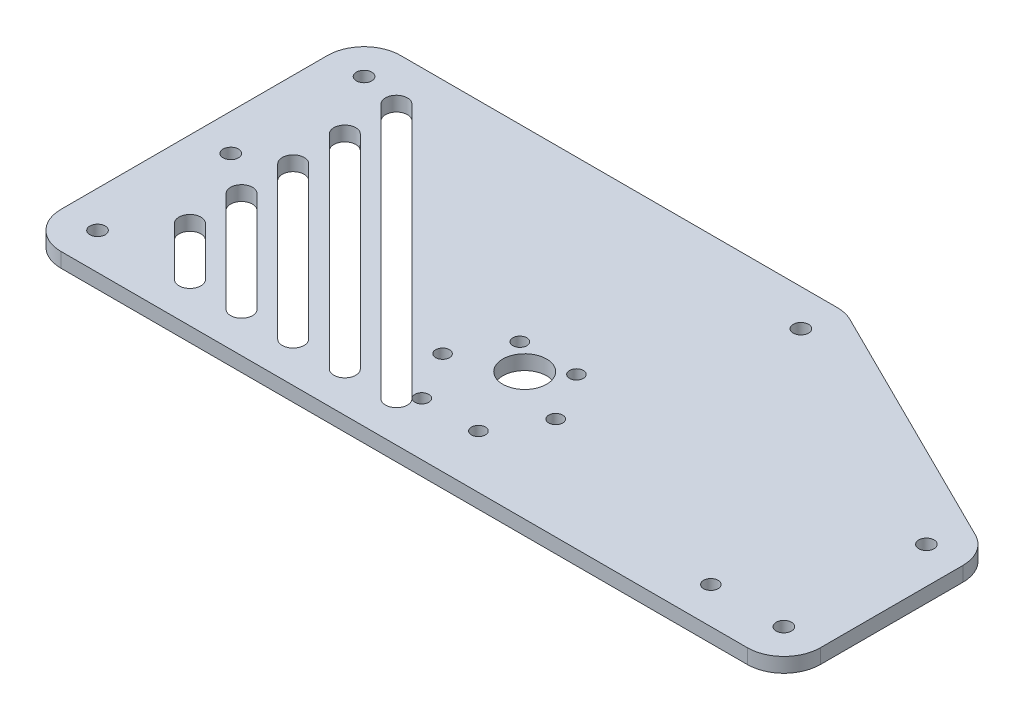
SolidWorks part; units mm, degrees
ref_plane "Front Plane" through (0, 0, 0) normal (1, 0, 0) x (0, 1, 0)
ref_plane "Top Plane" through (0, 0, 0) normal (0, 0, 1) x (0, 1, 0)
ref_plane "Right Plane" through (0, 0, 0) normal (0, 1, 0) x (-1, 0, 0)
sketch "Sketch1" plane through (0, 0, 0) normal (0, 1, 0) x (-1, 0, 0)
  line L3 (192.4493, -35) -> (72.7965, -35)
  line L4 (68.3472, -33.9557) -> (0, 0)
  line L6 (70.4493, 58) -> (70.4493, -35) construction
  line L7 (136.4493, 58) -> (136.4493, -35) construction
  line L8 (4.4493, 58) -> (70.4493, 58)
  line L9 (70.4493, 58) -> (136.4493, 58)
  line L10 (136.4493, 58) -> (192.4493, 58)
  line L11 (202.4493, 8) -> (-5.5507, 8) construction
  line L12 (-5.5507, 28) -> (202.4493, 28) construction
  line L13 (202.4493, 48) -> (202.4493, 28)
  line L14 (202.4493, 28) -> (202.4493, 8)
  line L15 (202.4493, 8) -> (202.4493, -25)
  line L16 (-5.5507, 48) -> (-5.5507, 28)
  line L17 (-5.5507, 28) -> (-5.5507, 8.9557)
  arc A0 (-5.5507, 48) -> (4.4493, 58) centre (4.4493, 48) cw
  arc A1 (-5.5507, 8.9557) -> (0, 0) centre (4.4493, 8.9557) ccw
  arc A3 (72.7965, -35) -> (68.3472, -33.9557) centre (72.7965, -25) cw
  arc A4 (202.4493, -25) -> (192.4493, -35) centre (192.4493, -25) cw
  arc A5 (192.4493, 58) -> (202.4493, 48) centre (192.4493, 48) cw
  point P16 (-5.5507, 58)
  point P19 (0, 0)
  point P27 (202.4493, -35)
  point P30 (202.4493, 58)
  dimension "D8" = 10
  dimension "D1" = 66
  dimension "D4" = 20
  dimension "D5" = 30
  dimension "D2" = 76
  dimension "D3" = 43
  dimension "D6" = 58
extrude "Boss-Extrude1" add sketch "Sketch1" along normal blind 4
sketch "Sketch2" plane through (0, 0, 0) normal (0, -1, 0) x (1, 0, 0)
  line L2 (-202.707, 11.5) -> (-191.0536, 11.5) construction
  line L3 (-118.9427, 30.8759) -> (-118.9427, 40.9875) construction
  line L4 (5.5507, 48) -> (5.5507, 8.9557) construction
  line L5 (-72.7965, -35) -> (-192.4493, -35) construction
  line L6 (-192.4493, 58) -> (-4.4493, 58) construction
  line L7 (-81.9427, 21.6542) -> (-81.9427, 50021.6542) construction
  line L9 (-181.4493, 19.5477) -> (-153.997, 47) construction
  line L10 (-183.5706, 21.669) -> (-156.1183, 49.1213)
  line L11 (-179.328, 17.4264) -> (-151.8757, 44.8787)
  line L12 (-181.4493, 5.4056) -> (-139.8549, 47) construction
  line L13 (-183.5706, 7.5269) -> (-141.9762, 49.1213)
  line L14 (-179.328, 3.2843) -> (-137.7335, 44.8787)
  line L15 (-181.4493, -8.7365) -> (-125.7127, 47) construction
  line L16 (-183.5706, -6.6152) -> (-127.8341, 49.1213)
  line L17 (-179.328, -10.8579) -> (-123.5914, 44.8787)
  line L18 (-181.4493, -22.8787) -> (-111.5706, 47) construction
  line L19 (-183.5706, -20.7574) -> (-113.6919, 49.1213)
  line L20 (-179.328, -25) -> (-109.4493, 44.8787)
  line L21 (-184.4493, 60.5499) -> (-184.4493, -43.895) construction
  line L22 (-186.5394, 50) -> (-97.1183, 50) construction
  line L23 (-108.5706, -40.8731) -> (-108.5706, -145.318) construction
  line L24 (-181.4493, 33.6899) -> (-168.1391, 47) construction
  line L25 (-165.6018, 31.1525) -> (-162.7734, 28.3241) construction
  line L26 (-158.5308, 24.0815) -> (-155.7023, 21.253) construction
  line L27 (-151.4597, 17.0104) -> (-148.6313, 14.182) construction
  line L28 (-183.5706, 35.8112) -> (-170.2605, 49.1213)
  line L29 (-179.328, 31.5685) -> (-166.0178, 44.8787)
  line L30 (-169.8445, 35.3952) -> (-172.6729, 38.2236) construction
  circle A0 centre (-192.4493, 48) radius 2.1
  circle A1 centre (-192.4493, -25) radius 2.1
  circle A2 centre (-192.4493, 11.5) radius 2.1
  circle A3 centre (-4.4493, 48) radius 2.1
  circle A4 centre (-4.4493, 8.9557) radius 2.1
  circle A5 centre (-72.7965, -25) radius 2.1
  circle A7 centre (-100.4427, 23) radius 6
  circle A9 centre (-100.4427, 30) radius 18.5 construction
  arc A11 (-183.5706, 21.669) -> (-179.328, 17.4264) centre (-181.4493, 19.5477) ccw
  arc A12 (-151.8757, 44.8787) -> (-156.1183, 49.1213) centre (-153.997, 47) ccw
  arc A13 (-183.5706, 7.5269) -> (-179.328, 3.2843) centre (-181.4493, 5.4056) ccw
  arc A14 (-137.7335, 44.8787) -> (-141.9762, 49.1213) centre (-139.8549, 47) ccw
  arc A15 (-183.5706, -6.6152) -> (-179.328, -10.8579) centre (-181.4493, -8.7365) ccw
  arc A16 (-123.5914, 44.8787) -> (-127.8341, 49.1213) centre (-125.7127, 47) ccw
  arc A17 (-183.5706, -20.7574) -> (-179.328, -25) centre (-181.4493, -22.8787) ccw
  arc A18 (-109.4493, 44.8787) -> (-113.6919, 49.1213) centre (-111.5706, 47) ccw
  arc A19 (-183.5706, 35.8112) -> (-179.328, 31.5685) centre (-181.4493, 33.6899) ccw
  arc A20 (-166.0178, 44.8787) -> (-170.2605, 49.1213) centre (-168.1391, 47) ccw
  circle A21 centre (-100.4427, 30) radius 15.5 construction
  circle A22 centre (-115.9427, 30) radius 1.9
  circle A23 centre (-108.1927, 43.4234) radius 1.9
  circle A24 centre (-92.6927, 43.4234) radius 1.9
  circle A25 centre (-84.9427, 30) radius 1.9
  circle A26 centre (-92.6927, 16.5766) radius 1.9
  circle A27 centre (-108.1927, 16.5766) radius 1.9
  circle A28 centre (-24.4493, 48) radius 2
  point P19 (-59.7454, 23)
  point P20 (-4.4493, 48)
  point P24 (-174.7942, 40.3449)
  point P27 (-24.4493, 79.1894)
  point P33 (-97.4924, -16.2986)
  point P37 (-24.4493, 47)
  point P45 (-167.7231, 33.2739)
  point P50 (-160.6521, 26.2028)
  point P57 (-153.581, 19.1317)
  point P64 (-146.5099, 12.0607)
  dimension "D5" = 30
  dimension "D1" = 4.2
  dimension "D14" = 31
  dimension "D15" = 3.8
  dimension "D2" = 37
  dimension "D6" = 12
  dimension "D7" = 45
  dimension "D8" = 6
  dimension "D9" = 8
  dimension "D10" = 8
  dimension "D11" = 4
  dimension "D12" = 10
  dimension "D13" = 7
  dimension "D4" = 80
  dimension "D16" = 6
extrude "Cut-Extrude1" cut sketch "Sketch2" against normal up to next
equation "\"MotorDriverLength\"= 60mm"
equation "\"MotorLength\"= 60"
equation "\"MotorDriverWidth\"=45"
equation "\"MotorWidth\"= 37"
equation "\"InnerWallThickness\"=3"
equation "\"BatteryWidth\"= 60"
equation "\"OutterWallThickness\"=4"
equation "\"CompartmentHeight\"=37"
equation "\"CompartmentWidth\"= \"MotorDriverLength\""
equation "\"MotorDiameter\"=37"
equation "\"D1@Sketch1\"=\"BatteryWidth\"+\"InnerWallThickness\"*2"
equation "\"BatteryHeight\"=24.2019"
equation "\"MotorDriverHeight\"=20"
equation "\"D4@Sketch1\"=\"MotorDriverHeight\""
equation "\"CircuitHeight\"=30"
equation "\"D5@Sketch1\"=\"CircuitHeight\""
equation "\"D2@Sketch1\"=\"MotorDriverLength\"+\"InnerWallThickness\"*2+\"FanThickness\""
equation "\"FanThickness\"= 10"
equation "\"FanHeight\"=50"
equation "\"D3@Sketch1\"=if(\"BatteryHeight\"  > \"MotorDiameter\", \"BatteryHeight\", \"MotorDiameter\") + \"InnerWallThickness\"*2"
equation "\"OuterWallThickness\"=4"
equation "\"D1@Boss-Extrude1\"=\"OuterWallThickness\""
equation "\"MotorShaftHole\"=12"
equation "\"D6@Sketch1\"=\"FanHeight\"+\"OutterWallThickness\"*2"
equation "\"BearingBore\"=4"
equation "\"MinShinWidth\"= 20"
equation "\"ShinThickness\"=10"
equation "\"PivotDistance\"=50"
equation "\"ThighLength\"= 200"
equation "\"HipBore\"=27"
equation "\"ThighThickness\"=30"
equation "\"MaxBending\"=135"
equation "\"MaxStretchingAngle\"= 140"
equation "\"ThighJointDistance\"=157.485"
equation "\"ShinLength\"=100"
equation "\"BearingDiameter\"= 10"
equation "\"D2@Sketch2\"=\"MotorDiameter\""
equation "\"D3@Sketch2\"=\"BearingBore\""
equation "\"D4@Sketch2\"=\"PivotDistance\"*1.6"
equation "\"D6@Sketch2\"=\"MotorShaftHole\""
